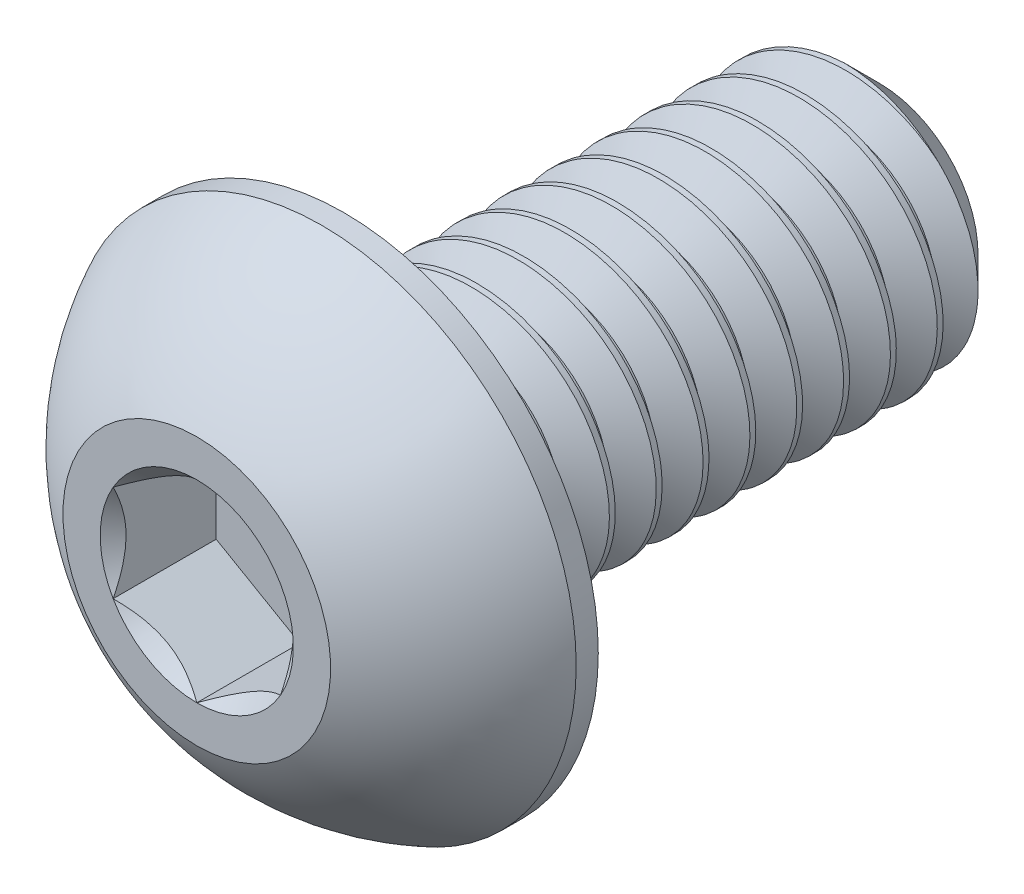
SolidWorks part; units mm, degrees
note: '?' marks a value the reader was unsure of.
ref_plane "Front" through (0, 0, 0) normal (0, 0, 1) x (1, 0, 0)
ref_plane "Top" through (0, 0, 0) normal (0, 1, 0) x (1, 0, 0)
ref_plane "Right" through (0, 0, 0) normal (1, 0, 0) x (0, 0, -1)
sketch "Sketch1" plane through (0, 0, 0) normal (1, 0, 0) x (0, 0, -1)
  line L2 (2.2, 2) -> (10.2, 2)
  line L3 (10.2, 2) -> (10.2, 0)
  line L4 (10.2, 0) -> (2.2, 0)
  line L6 (1.87, 3.8) -> (2.2, 3.8) construction
  line L7 (10.2, 2) -> (10.2, -2) construction
  line L8 (0, 0) -> (2.2, 0) construction
  line L9 (2.2, 3.8) -> (2.2, -3.8) construction
  line L11 (2.2, 2) -> (2.2, 0)
  line L13 (0, 1.25) -> (0, -1.25) construction
  line L14 (0, 1.25) -> (0, 2) construction
  arc A3 (0, 2) -> (1.87, 3.8) centre (3.7264, 0) cw construction
  dimension "D1" = 0.33
  dimension "Head Ht" = 2.2
  dimension "Head Dia" = 7.6
  dimension "Dia" = 4
  dimension "Lg" = 8
  dimension "Hex" = 2.5
revolve "Revolve1" add sketch "Sketch1" angle 360 mid plane about L4
sketch "Sketch3" plane through (0, 0, -10.2) normal (0, 0, -1) x (-1, 0, 0)
  circle A0 centre (0, 0) radius 2
curve "Helix/Spiral1" pitch 0.7 height 8.7 turns 12.4286
chamfer "Chamfer1" distance 0.525 angle 45 1 edges at (0, 2, -10.2)
sketch "Sketch7" plane through (0, 0, 0) normal (1, 0, 0) x (0, 0, -1)
  line L6 (1.87, 3.8) -> (2.2, 3.8) construction
  line L8 (0, 0) -> (2.2, 0) construction
  line L11 (2.2, 3.8) -> (2.2, -3.8) construction
  line L12 (1.87, 3.8) -> (2.2, 3.8)
  line L13 (0, 0) -> (2.2, 0)
  line L14 (0, 1.25) -> (0, -1.25) construction
  line L15 (2.2, 3.8) -> (2.2, 0)
  line L16 (0, 2) -> (0, 0)
  arc A2 (1.87, 3.8) -> (0, 2) centre (3.7264, 0) ccw construction
  arc A3 (1.87, 3.8) -> (0, 2) centre (3.7264, 0) ccw
revolve "Revolve2" add sketch "Sketch7" angle 360 mid plane about L13
sketch "Sketch5" plane through (0, 0, 0) normal (0, 0, 1) x (1, 0, 0)
  line L1 (1.25, -0.7217) -> (1.25, 0.7217)
  line L2 (1.25, 0.7217) -> (0, 1.4434)
  line L3 (0, 1.4434) -> (-1.25, 0.7217)
  line L4 (-1.25, 0.7217) -> (-1.25, -0.7217)
  line L5 (-1.25, -0.7217) -> (0, -1.4434)
  line L6 (0, -1.4434) -> (1.25, -0.7217)
  circle A0 centre (0, 0) radius 1.25 construction
extrude "Cut-Extrude2" cut sketch "Sketch5" against normal blind 1.54
sketch "Sketch6" plane through (0, 0, 0) normal (0, 0, 1) x (1, 0, 0)
  circle A0 centre (0, 0) radius 1.4434
extrude "Cut-Extrude3" cut sketch "Sketch6" against normal blind 1.54 draft 45
sketch "Sketch2" plane through (0, 0, 0) normal (1, 0, 0) x (0, 0, -1)
  line L0 (9.675, 2) -> (10.2875, 2)
  line L1 (10.2875, 2) -> (10.025, 1.5453)
  line L2 (10.025, 1.5453) -> (9.9375, 1.5453)
  line L3 (9.9375, 1.5453) -> (9.675, 2)
  line L4 (9.8063, 1.7727) -> (10.1562, 1.7727) construction
  dimension "D1" = 60
  dimension "D2" = 0.0875
  dimension "D3" = 0.35
sweep "Cut-Sweep1" cut profiles "Sketch2" path "Helix/Spiral1"
sketch "Sketch10" plane through (0, 0, 0) normal (1, 0, 0) x (0, 0, -1)
  line L0 (10.2, 2) -> (10.2, -2) construction
  point P0 (9.15, -2)
  dimension "D1" = 1.05
ref_axis "Center Axis 1" through (0, 0, -8.1113) along (0, 0, 1)?
ref_plane "Contact Plane 1" through (0, 0, -2.2) normal (0, 0, -1) x (-1, 0, 0)
ref_plane "Contact Plane 2" through (0, 0, 0) normal (0, 0, 1) x (1, 0, 0)
equation "\"D3@Helix/Spiral1\" = \"Lg@Sketch1\" + \"D4@Helix/Spiral1\""
equation "\"D2@Sketch2\" = \"D4@Helix/Spiral1\" * .125"
equation "\"D3@Sketch2\" = \"D4@Helix/Spiral1\" * .5"
equation "\"D1@Chamfer1\" = \"D4@Helix/Spiral1\" * .75"
equation "\"D1@Cut-Extrude2\" = \"Head Ht@Sketch1\" * .7"
equation "\"D1@Sketch1\" = \"Head Ht@Sketch1\" * .15"
equation "\"D1@Sketch10\" = \"D4@Helix/Spiral1\" * 1.5"
equation "\"D1@Cut-Extrude3\" = \"D1@Cut-Extrude2\""
